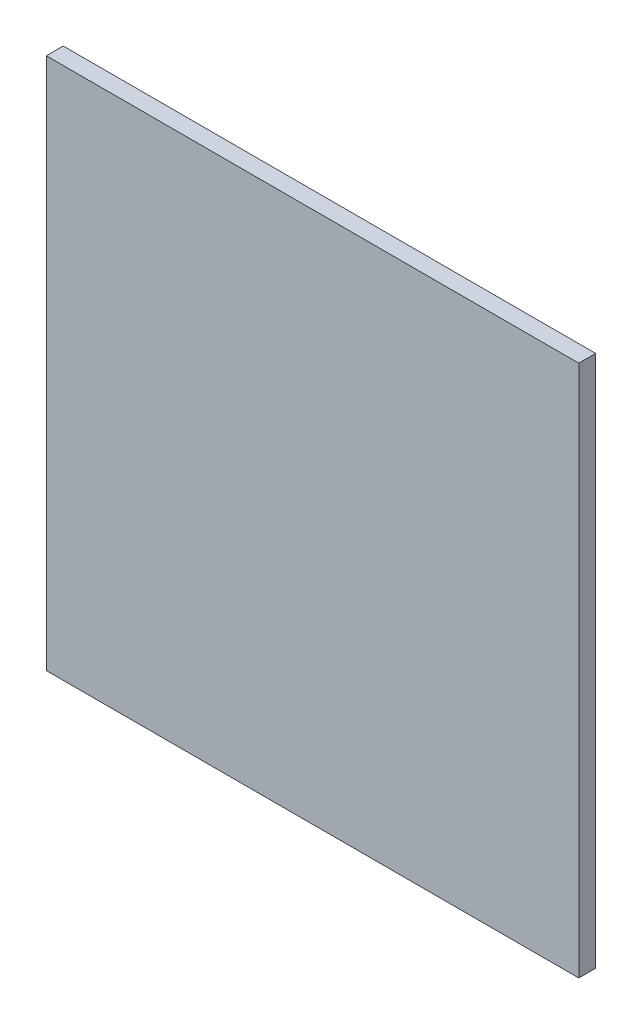
SolidWorks part; units mm, degrees
ref_plane "Front Plane" through (0, 0, 0) normal (0, 0, 1) x (1, 0, 0)
ref_plane "Top Plane" through (0, 0, 0) normal (0, 1, 0) x (1, 0, 0)
ref_plane "Right Plane" through (0, 0, 0) normal (1, 0, 0) x (0, 0, -1)
sketch "Sketch1" plane through (0, 0, 0) normal (0, 0, 1) x (1, 0, 0)
  line L1 (-300, 300) -> (300, 300)
  line L2 (-300, 300) -> (-300, -300)
  line L3 (-300, -300) -> (300, -300)
  line L4 (300, 300) -> (300, -300)
  dimension "D1" = 600
extrude "Boss-Extrude1" add sketch "Sketch1" along normal blind 19.05
